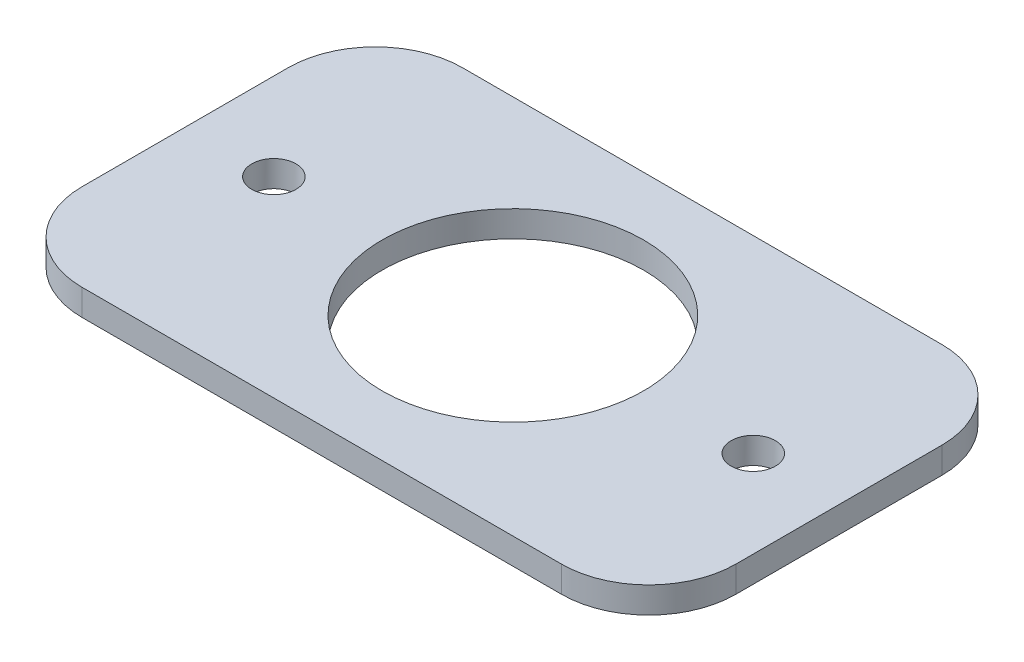
SolidWorks part; units mm, degrees
ref_plane "前视基准面" through (0, 0, 0) normal (0, 0, 1) x (1, 0, 0)
ref_plane "上视基准面" through (0, 0, 0) normal (0, 1, 0) x (1, 0, 0)
ref_plane "右视基准面" through (0, 0, 0) normal (1, 0, 0) x (0, 0, -1)
sketch "草图1" plane through (0, 0, 0) normal (0, 1, 0) x (1, 0, 0)
  line L1 (65.0822, 33.7204) -> (-9.9178, 33.7204)
  line L2 (65.0822, 33.7204) -> (65.0822, -9.9178)
  line L3 (65.0822, -9.9178) -> (-9.9178, -9.9178)
  line L4 (-9.9178, 33.7204) -> (-9.9178, -9.9178)
base flange "基体-法兰1" sketch "草图1" thickness 3 reverse thickness direction no parameters "D1"=0.762
sketch "草图8" plane through (0, -3, 0) normal (0, -1, 0) x (-1, 0, 0)
  line L0 (9.9178, 33.7204) -> (9.9178, -9.9178) construction
  circle A0 centre (-27.5822, 12) radius 15
  point P2 (0, 0)
  dimension "D1" = 37.5
extrude "切除-拉伸1" cut sketch "草图8" against normal through all normal cut yes
fillet "圆角1" radius 10 4 edges at (65.0822, -1.5, -33.7204) (-9.9178, -1.5, -33.7204) (65.0822, -1.5, 9.9178) (-9.9178, -1.5, 9.9178)
sketch "草图9" plane through (0, 0, 0) normal (0, 1, 0) x (1, 0, 0)
  line L0 (-9.9178, 23.7204) -> (-9.9178, 0.0822) construction
  line L3 (0.0822, -9.9178) -> (55.0822, -9.9178) construction
  line L4 (65.0822, 0.0822) -> (65.0822, 23.7204) construction
  circle A0 centre (0.0822, 12.0822) radius 2.54
  circle A1 centre (55.0822, 12.0822) radius 2.54
  dimension "D1" = 10
  dimension "D3" = 10
  dimension "D2" = 22
extrude "切除-拉伸2" cut sketch "草图9" against normal blind 10 normal cut yes
sketch "折弯-线1" plane through (0, 0, 0) normal (0, 1, 0) x (1, 0, 0)
sketch "边界框1" plane through (0, 0, 0) normal (0, 1, 0) x (1, 0, 0)
sheet metal parameters "钣金7" thickness 3 parameters "D1"=0.762
flat pattern "平板型式7" [suppressed]
sketch "折弯-线2" plane through (0, 0, 0) normal (0, 1, 0) x (1, 0, 0)
sketch "边界框2" [suppressed] plane through (0, 0, 0) normal (0, 1, 0) x (1, 0, 0)
sheet metal parameters "钣金8" thickness 3 parameters "D1"=0.762
flat pattern "平板型式7"
sketch "折弯-线2" plane through (0, 0, 0) normal (0, 1, 0) x (1, 0, 0)
sketch "边界框2" [suppressed] plane through (0, 0, 0) normal (0, 1, 0) x (1, 0, 0)
sheet metal parameters "钣金9" thickness 3 parameters "D1"=0.762
flat pattern "平板型式7"
sketch "折弯-线2" plane through (0, 0, 0) normal (0, 1, 0) x (1, 0, 0)
sketch "边界框2" [suppressed] plane through (0, 0, 0) normal (0, 1, 0) x (1, 0, 0)
